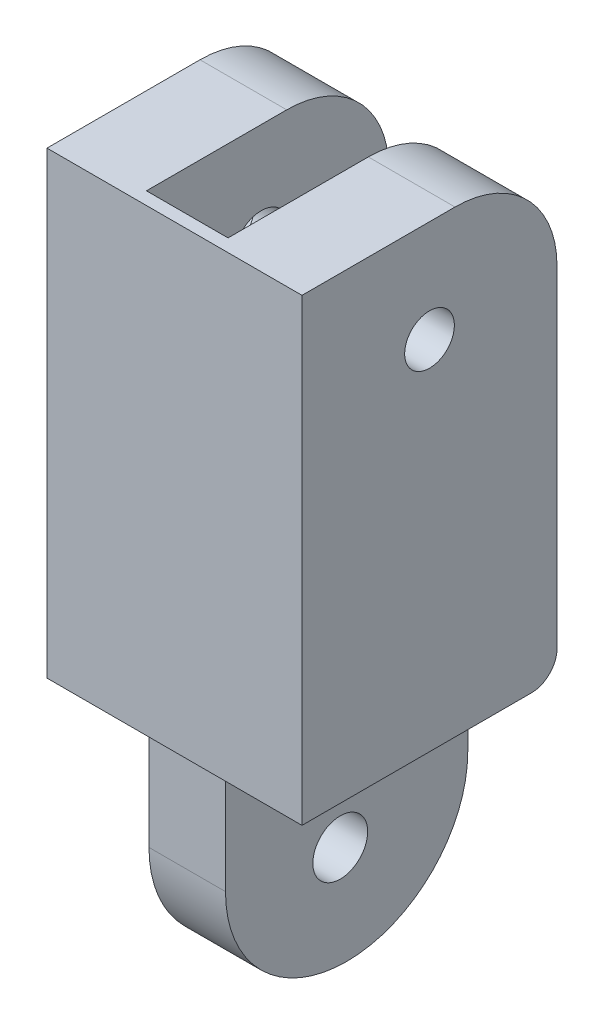
SolidWorks part; units mm, degrees
ref_plane "Plan de face" through (0, 0, 0) normal (0, 0, 1) x (1, 0, 0)
ref_plane "Plan de dessus" through (0, 0, 0) normal (0, 1, 0) x (1, 0, 0)
ref_plane "Plan de droite" through (0, 0, 0) normal (1, 0, 0) x (0, 0, -1)
sketch "Esquisse1" plane through (0, 0, 0) normal (0, 0, 1) x (1, 0, 0)
  line L1 (-5, -9) -> (5, -9)
  line L2 (-5, -9) -> (-5, 9)
  line L3 (-5, 9) -> (5, 9)
  line L4 (5, -9) -> (5, 9)
  line L5 (-5, -9) -> (5, 9) construction
  line L6 (-5, 9) -> (5, -9) construction
  line L7 (-1.5, -9) -> (1.5, -9)
  line L8 (-1.5, -9) -> (-1.5, -18)
  line L9 (-1.5, -18) -> (1.5, -18)
  line L10 (1.5, -9) -> (1.5, -18)
  point P0 (0, 0)
  point P10 (0, -18)
  dimension "D1" = 10
  dimension "D2" = 18
  dimension "D3" = 3
  dimension "D4" = 9
extrude "Boss.-Extru.1" add sketch "Esquisse1" along normal blind 10 contours L1 L4 L3 L2 | L10 L1 L8 L9 region at (0, 0, 0) region at (0, -13.5, 0)
sketch "Esquisse4" plane through (-5, 0, 0) normal (-1, 0, 0) x (0, 0, 1)
  line L0 (10, 9) -> (0, 9) construction
  circle A0 centre (5, 5) radius 0.975
  point P4 (5, 9)
  dimension "D1" = 1.95
  dimension "D2" = 4
extrude "Enlèv. mat.-Extru.3" cut sketch "Esquisse4" against normal blind 10
sketch "Esquisse5" plane through (0, 0, 0) normal (1, 0, 0) x (0, 0, -1)
  line L10 (-10, 9) -> (0, 9) construction
  line L11 (-9.5, 9) -> (0, 9)
  line L12 (-9.5, 9) -> (-9.5, 4)
  line L13 (-9.5, 4) -> (0, 4)
  line L14 (0, 9) -> (0, 4)
  line L15 (0, -9) -> (0, 9) construction
  line L16 (-10, -9) -> (-10, 9) construction
  arc A2 (-9.5, 4) -> (0, 4) centre (-4.75, 4) ccw
  dimension "D1" = 0.5
  dimension "D2" = 5
extrude "Enlèv. mat.-Extru.4" cut sketch "Esquisse5" against normal mid plane 3.2 contours L13 A2 | L14 L11 L12 L13 region at (0, 6.5, 4.75) region at (0, 1.984, 4.75)
fillet "Congé4" radius 0.3 1 edges at (0, 4, 0)
sketch "Esquisse6" plane through (1.5, 0, 0) normal (1, 0, 0) x (0, 0, -1)
  line L0 (-10, -18) -> (0, -18) construction
  line L1 (-10, -9) -> (-9.5, -9)
  line L2 (-10, -9) -> (-10, -18)
  line L3 (-10, -18) -> (-9.5, -18)
  line L4 (-9.5, -9) -> (-9.5, -18)
  line L5 (-9.5, -9) -> (0, -9) construction
  line L6 (0, -9) -> (0, -18) construction
  line L7 (0, -13.25) -> (0, -18)
  line L8 (0, -18) -> (-9.5, -18)
  circle A0 centre (-5, -14) radius 1.075
  arc A1 (-9.5, -13.25) -> (0, -13.25) centre (-4.75, -13.25) ccw
  point P15 (0, 0)
  point P21 (-9.5, -15.8966)
  point P22 (0, 0)
  point P24 (0, 0)
  point P25 (0, 0)
  line M7 (0, -18) -> (0, -9)
  line M8 (0, -9) -> (-10, -9)
  line M9 (-10, -9) -> (-10, -18)
  line M10 (-10, -18) -> (0, -18)
  dimension "D3" = 2.15
  dimension "D1" = 0.5
  dimension "D2" = 4
  dimension "D4" = 4.5
extrude "Enlèv. mat.-Extru.5" cut sketch "Esquisse6" against normal through all contours L4 M8 M9 M10 | A1 L4 M10 | A1 L8 M7 | A0 region at (1.5, -13.5, 9.75) region at (1.5, -16.939, 8.439) region at (1.5, -16.939, 1.061) region at (1.5, -14, 5)
fillet "Congé5" radius 4 2 edges at (-3.3, 9, 0) (3.3, 9, 0)
fillet "Congé6" radius 1 2 edges at (-3.25, -9, 0) (3.25, -9, 0)
sketch "Esquisse7" plane through (-5, 0, 0) normal (-1, 0, 0) x (0, 0, 1)
  circle A0 centre (5, 5) radius 1.075
  dimension "D1" = 2.15
extrude "Enlèv. mat.-Extru.6" cut sketch "Esquisse7" against normal up to next
sketch "Esquisse8" plane through (-5, 0, 0) normal (-1, 0, 0) x (0, 0, 1)
  circle A0 centre (5, 5) radius 1.925
  dimension "D1" = 3.85
extrude "Enlèv. mat.-Extru.7" cut sketch "Esquisse8" against normal blind 2.05
